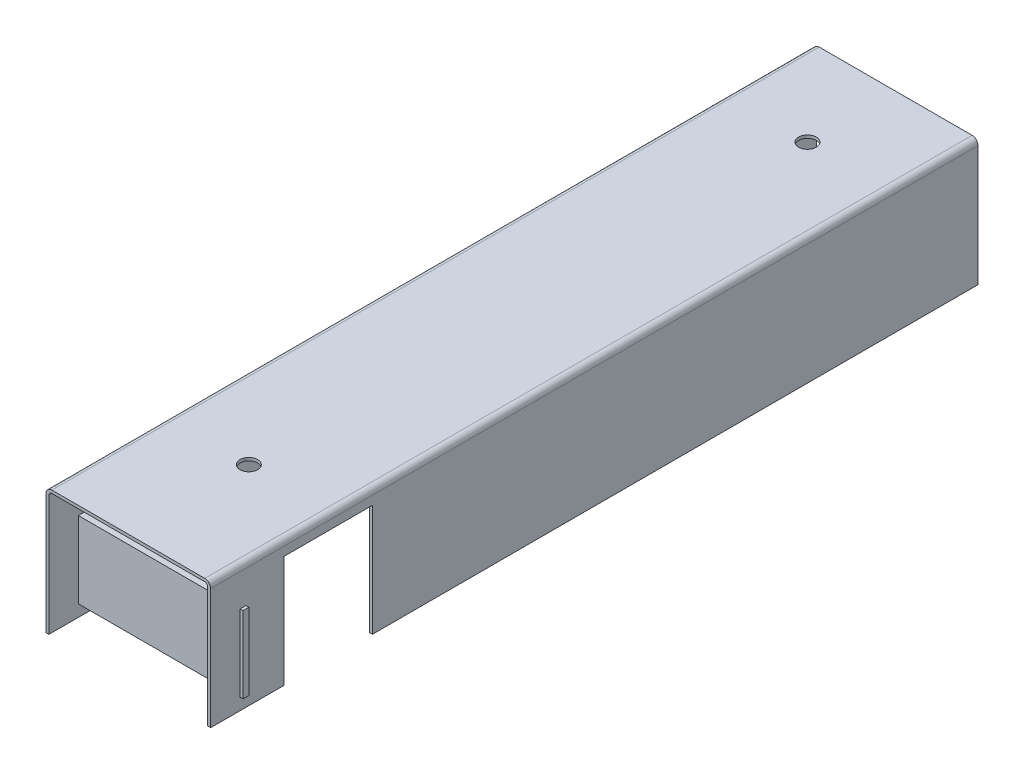
SolidWorks part; units mm, degrees
ref_plane "Płaszczyzna przednia" through (0, 0, 0) normal (0, 0, 1) x (1, 0, 0)
ref_plane "Płaszczyzna górna" through (0, 0, 0) normal (0, 1, 0) x (1, 0, 0)
ref_plane "Płaszczyzna prawa" through (0, 0, 0) normal (1, 0, 0) x (0, 0, -1)
sketch "Sketch1" plane through (0, 0, 0) normal (0, 0, 1) x (1, 0, 0)
  line L0 (26.6977, -20.5) -> (27, -20.5)
  line L1 (-28, 21.5) -> (28, 21.5)
  line L2 (-28, 21.5) -> (-28, -21.5)
  line L4 (28, 21.5) -> (28, -21.5)
  line L5 (-28, 21.5) -> (28, -21.5) construction
  line L6 (-28, -21.5) -> (28, 21.5) construction
  line L7 (-27, 20.5) -> (27, 20.5)
  line L8 (-27, 20.5) -> (-27, -20.5)
  line L9 (-27, -20.5) -> (-26.6977, -20.5)
  line L10 (27, 20.5) -> (27, -20.5)
  line L11 (-27, 20.5) -> (27, -20.5) construction
  line L12 (-27, -20.5) -> (27, 20.5) construction
  line L13 (-28, -21.5) -> (-27, -21.5)
  line L14 (-27, -21.5) -> (-27, -20.5)
  line L15 (28, -21.5) -> (27, -21.5)
  line L16 (27, -21.5) -> (27, -20.5)
  point P0 (0, 0)
  point P6 (0, 0)
  dimension "D1" = 56
  dimension "D2" = 43
  dimension "D3" = 54
  dimension "D4" = 41
extrude "Boss-Extrude1" add sketch "Sketch1" along normal blind 261 contours L16 L15 L4 L1 L2 L13 L14 L8 L7 L10 region at (0, 20.794, 0)
fillet "Fillet1" radius 2 2 edges at (-28, 21.5, 130.5) (28, 21.5, 130.5)
fillet "Fillet2" radius 1 2 edges at (27, 20.5, 130.5) (-27, 20.5, 130.5)
sketch "Sketch2" plane through (-27, 0, 0) normal (1, 0, 0) x (0, 0, -1)
  line L0 (-251, -21.5) -> (-251, 19.5) construction
  line L1 (-261, -21.5) -> (0, -21.5) construction
  line L2 (0, 19.5) -> (-261, 19.5) construction
  line L3 (-261, 19.5) -> (-261, -21.5) construction
  line L4 (-251, -17.5) -> (-261, -17.5) construction
  line L10 (-251, -17.5) -> (-249, -17.5)
  line L11 (-251, -17.5) -> (-251, 8.5)
  line L12 (-251, 8.5) -> (-249, 8.5)
  line L13 (-249, -17.5) -> (-249, 8.5)
  line L14 (-251, -17.5) -> (-249, 8.5) construction
  line L15 (-251, 8.5) -> (-249, -17.5) construction
  point P14 (-250, -4.5)
  dimension "D1" = 10
  dimension "D2" = 4
  dimension "D3" = 2
  dimension "D4" = 26
extrude "Boss-Extrude2" add sketch "Sketch2" along normal blind 56 and the other way blind 2
sketch "Sketch3" plane through (0, 21.5, 0) normal (0, 1, 0) x (1, 0, 0)
  line L0 (0, 0) -> (0, -261) construction
  line L1 (-26, 0) -> (26, 0) construction
  line L2 (-26, -261) -> (26, -261) construction
  circle A0 centre (0, -30) radius 3
  circle A1 centre (0, -220) radius 3
  dimension "D1" = 30
  dimension "D2" = 41
extrude "Cut-Extrude1" cut sketch "Sketch3" against normal blind 11
sketch "Sketch4" plane through (28, 0, 0) normal (1, 0, 0) x (0, 0, -1)
  line L0 (-261, 21.5) -> (0, 21.5) construction
  line L1 (-236, 16.5) -> (-206, 16.5)
  line L2 (-236, 16.5) -> (-236, -23.5)
  line L3 (-236, -23.5) -> (-206, -23.5)
  line L4 (-206, 16.5) -> (-206, -23.5)
  line L5 (-236, 16.5) -> (-206, -23.5) construction
  line L6 (-236, -23.5) -> (-206, 16.5) construction
  line L7 (-261, 19.5) -> (-261, -21.5) construction
  point P4 (-221, -3.5)
  dimension "D1" = 40
  dimension "D2" = 30
  dimension "D3" = 5
  dimension "D4" = 25
extrude "Cut-Extrude2" cut sketch "Sketch4" against normal blind 10
sketch "Sketch5" plane through (28, 0, 0) normal (1, 0, 0) x (0, 0, -1)
  line L0 (-261, 19.5) -> (-261, -21.5) construction
  line L1 (-206, -21.5) -> (0, -21.5) construction
  circle A0 centre (-108.5, -5.5) radius 3.5
  circle A1 centre (-88.5, -5.5) radius 3.5
  dimension "D3" = 16
  dimension "D1" = 152.5
  dimension "D2" = 172.5
  dimension "D4" = 16
